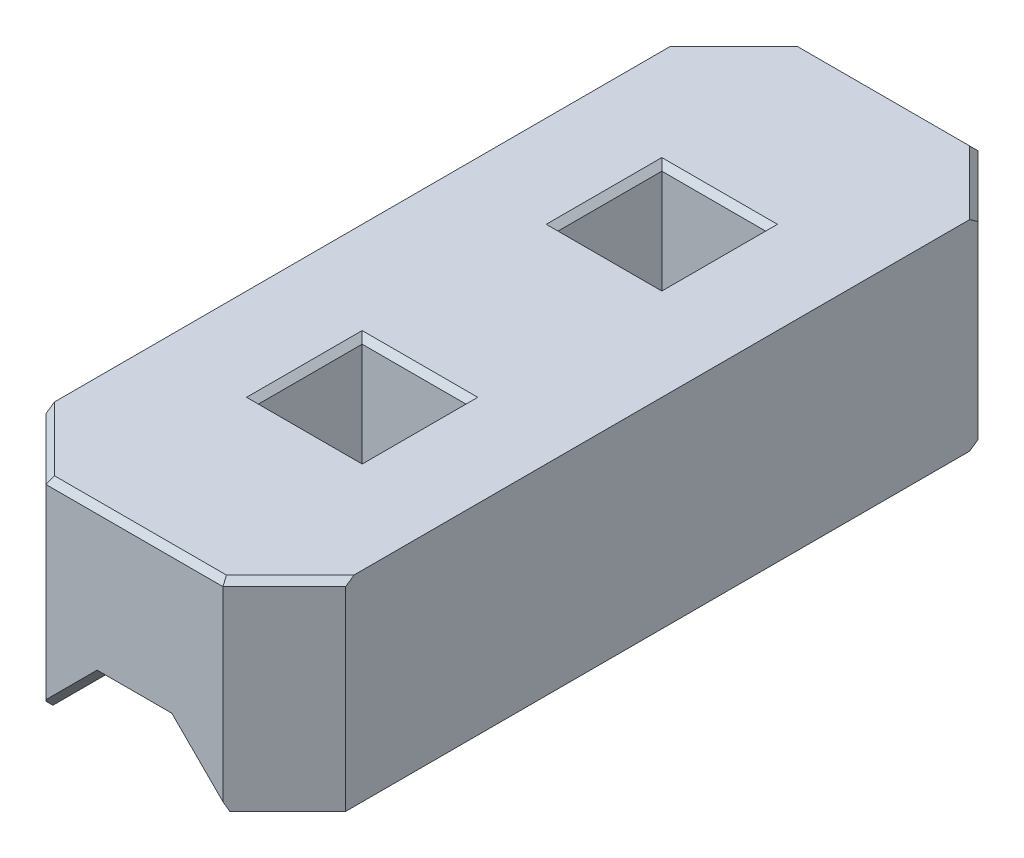
SolidWorks part; units mm, degrees
ref_plane "前视基准面" through (0, 0, 0) normal (0, 0, 1) x (1, 0, 0)
ref_plane "上视基准面" through (0, 0, 0) normal (0, 1, 0) x (1, 0, 0)
ref_plane "右视基准面" through (0, 0, 0) normal (1, 0, 0) x (0, 0, -1)
sketch "Sketch5" plane through (0, 0, 0) normal (0, 1, 0) x (1, 0, 0)
  line L0 (0, 1.6) -> (0, -2.0978) construction
  line L1 (-0.375, 1.6) -> (0.375, 1.6)
  line L2 (-0.635, 1.34) -> (-0.635, -1.34)
  line L3 (-0.375, -1.6) -> (0.375, -1.6)
  line L4 (0.635, 1.34) -> (0.635, -1.34)
  line L5 (-0.635, 1.6) -> (0.635, -1.6) construction
  line L6 (-0.635, -1.6) -> (0.635, 1.6) construction
  line L7 (-0.635, 0) -> (0.635, 0) construction
  line L8 (-0.22, 0.855) -> (0.22, 0.855)
  line L9 (-0.22, 0.855) -> (-0.22, 0.415)
  line L10 (-0.22, 0.415) -> (0.22, 0.415)
  line L11 (0.22, 0.855) -> (0.22, 0.415)
  line L12 (-0.22, 0.855) -> (0.22, 0.415) construction
  line L13 (-0.22, 0.415) -> (0.22, 0.855) construction
  line L14 (-0.22, -0.415) -> (0.22, -0.415)
  line L15 (0.22, -0.855) -> (0.22, -0.415)
  line L16 (-0.22, -0.855) -> (0.22, -0.855)
  line L17 (-0.22, -0.855) -> (-0.22, -0.415)
  line L18 (-0.635, 1.34) -> (-0.375, 1.6)
  line L19 (0.375, 1.6) -> (0.635, 1.34)
  line L20 (-0.635, -1.34) -> (-0.375, -1.6)
  line L21 (0.375, -1.6) -> (0.635, -1.34)
  point P0 (0, 0)
  point P8 (0, 0.635)
  point P28 (0.635, 0)
  point P29 (0, 0)
  point P30 (0, 0)
  point P31 (0, 0)
  point P32 (-0.635, 0)
  point P33 (-0.0433, 1.5245)
  point P34 (0, 1.6)
  dimension "D1" = 1.27
  dimension "D2" = 3.2
  dimension "D3" = 1.27
  dimension "D4" = 0.44
  dimension "D5" = 0.44
extrude "Boss-Extrude1" add sketch "Sketch5" along normal blind 0.85
sketch "Sketch6" plane through (0, 0, 1.6) normal (0, 0, 1) x (1, 0, 0)
  line L0 (0, 0.85) -> (0, 0) construction
  line L1 (-0.375, 0.85) -> (0.375, 0.85) construction
  line L2 (-0.375, 0) -> (-0.148, 0.227)
  line L3 (-0.148, 0.227) -> (0.148, 0.227)
  line L4 (-0.375, 0) -> (0.375, 0)
  line L5 (0.375, 0) -> (0.148, 0.227)
  point P10 (0, 0.227)
  dimension "D1" = 0.227
  dimension "D2" = 45
extrude "Cut-Extrude1" cut sketch "Sketch6" against normal up to surface (3.2 mm away) up to face at (0, 0.425, -1.6)
chamfer "Chamfer1" distance 0.025 angle 45 23 edges at (0, 0.85, 0.855) (0.22, 0.85, 0.635) (0, 0.85, 0.415) (-0.22, 0.85, 0.635) (0, 0.85, -1.6) (0.505, 0.85, -1.47) (0.505, 0.85, 1.47) (0, 0.85, 1.6) (-0.505, 0.85, 1.47) (-0.505, 0.85, -1.47) (0, 0.85, -0.855) (-0.22, 0.85, -0.635) (0, 0.85, -0.415) (0.22, 0.85, -0.635) (0, 0.227, 1.6) (0, 0.227, -1.6) (0.2615, 0.1135, 1.6) (-0.2615, 0.1135, 1.6) (-0.505, 0, 1.47) (0.505, 0, -1.47) (0.2615, 0.1135, -1.6) (-0.505, 0, -1.47) (-0.2615, 0.1135, -1.6)
